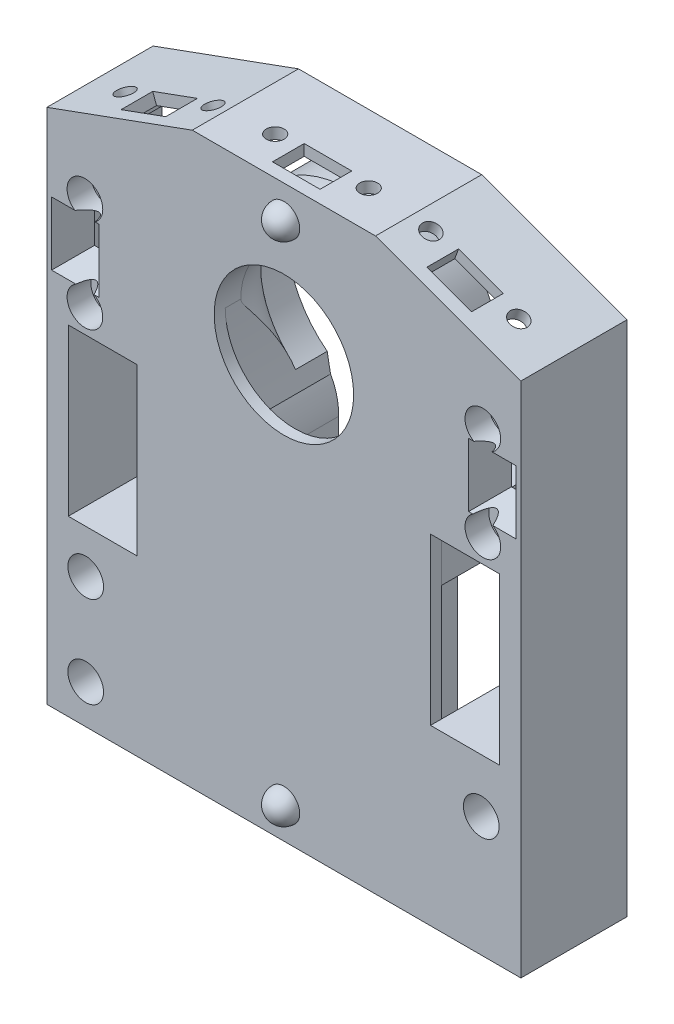
SolidWorks part; units mm, degrees
ref_plane "Front Plane" through (0, 0, 0) normal (0, 0, 1) x (1, 0, 0)
ref_plane "Top Plane" through (0, 0, 0) normal (0, 1, 0) x (1, 0, 0)
ref_plane "Right Plane" through (0, 0, 0) normal (1, 0, 0) x (0, 0, -1)
sketch "Sketch1" plane through (0, 0, 0) normal (0, 0, 1) x (1, 0, 0)
  line L5 (-16.4, -18.5) -> (43.4, -18.5)
  line L6 (-16.4, -18.5) -> (-16.4, 46.724)
  line L8 (43.4, -18.5) -> (43.4, 46.724)
  line L9 (1.9423, 53.4) -> (-16.4, 46.724)
  line L10 (1.9423, 53.4) -> (25.0577, 53.4)
  line L11 (-5, 24.3) -> (-5, 3.4)
  line L12 (25.0577, 53.4) -> (43.4, 46.724)
  line L13 (2.1891, 52) -> (24.8109, 52)
  line L14 (-15, -17.1) -> (42, -17.1) construction
  line L15 (-15, 30.4) -> (-15, -17.1) construction
  line L16 (42, -17.1) -> (42, 30.4) construction
  line L17 (-6.5, 21.65) -> (33.5, 21.65) construction
  line L18 (21.2, 52) -> (5.8, 52) construction
  line L19 (-13.9, 46.144) -> (2.1891, 52)
  line L20 (-15, 40.9) -> (-0.8, 40.9) construction
  line L21 (24.8109, 52) -> (40.9, 46.144)
  line L22 (27.8, 40.9) -> (42, 40.9) construction
  line L23 (-13.9, 46.144) -> (-13.9, 42.1)
  line L24 (-13.9, 42.1) -> (-5, 42.1)
  line L25 (-5, 42.1) -> (-5, 24.3)
  line L26 (-5, 24.3) -> (-13.7, 24.3)
  line L27 (-13.7, 24.3) -> (-13.7, 3.4)
  line L28 (-13.7, 3.4) -> (-5, 3.4)
  line L29 (-5, 18) -> (-5, 0) construction
  line L30 (-5, 3.4) -> (-5, -17.1)
  line L31 (-5, -17.1) -> (32, -17.1)
  line L32 (32, -17.1) -> (32, 3.4)
  line L33 (32, 18) -> (32, 0) construction
  line L34 (32, 3.4) -> (40.7, 3.4)
  line L35 (40.7, 3.4) -> (40.7, 24.3)
  line L36 (40.7, 24.3) -> (32, 24.3)
  line L37 (32, 24.3) -> (32, 42.1)
  line L38 (32, 42.1) -> (40.9, 42.1)
  line L39 (40.9, 42.1) -> (40.9, 46.144)
  line L52 (-15, 25.5) -> (-15, 40.9) construction
  line L53 (42, 40.9) -> (42, 25.5) construction
  line L54 (-13, 15.5) -> (-13, 12.5) construction
  line L55 (-0.8, 25.5) -> (-15, 25.5) construction
  line L56 (42, 25.5) -> (27.8, 25.5) construction
  line L57 (40, 15.118) -> (40, 12.882) construction
  line L58 (-5, 24.3) -> (2.2578, 24.3)
  line L59 (-5, 24.3) -> (-5, 18)
  line L60 (5, 18) -> (5, -17.1)
  line L61 (5, -17.1) -> (22, -17.1)
  line L62 (22, -17.1) -> (22, 18)
  line L63 (32, 24.3) -> (32, 3.4)
  line L64 (-5, 18) -> (5, 18)
  line L65 (-5, 23.5) -> (-5, 4.5) construction
  line L66 (22, 18) -> (32, 18)
  line L67 (32, 18) -> (32, 24.3)
  line L68 (32, 24.3) -> (24.7422, 24.3)
  arc A0 (27.3, 34.65) -> (-0.3, 34.65) centre (13.5, 34.65) ccw
  circle A1 centre (13.5, 34.65) radius 12.5 construction
  arc A2 (27.3, 34.65) -> (23.1, 21.65) centre (5.081, 34.65) cw
  arc A3 (22, 18) -> (23.1, 21.65) centre (27.8389, 18.2311) cw
  arc A4 (-0.3, 34.65) -> (3.9, 21.65) centre (21.919, 34.65) ccw
  arc A5 (3.9, 21.65) -> (5, 18) centre (-0.8389, 18.2311) cw
  point P2 (13.5, 52)
  point P5 (13.5, 53.4)
  dimension "D28" = 1.3
  dimension "D30" = 20.3
  dimension "D1" = 1.4
  dimension "D2" = 1.4
  dimension "D3" = 1.4
  dimension "D4" = 70
  dimension "D5" = 18.3423
  dimension "D6" = 70
  dimension "D7" = 18.3423
  dimension "D12" = 22.6217
  dimension "D13" = 160
  dimension "D14" = 160
  dimension "D15" = 2.5
  dimension "D16" = 2.5
  dimension "D17" = 0
  dimension "D18" = 1.2
  dimension "D19" = 1.2
  dimension "D20" = 10
  dimension "D21" = 10
  dimension "D22" = 0.7
  dimension "D23" = 1.2
  dimension "D24" = 1.2
  dimension "D25" = 0.7
  dimension "D26" = 20.5
  dimension "D27" = 20.5
  dimension "D29" = 20.3
sketch "Sketch2" plane through (19.6148, 53.8912, 0) normal (0.342, 0.9397, 0) x (0.9397, -0.342, 0)
  line L0 (15.4737, 3.2) -> (15.4737, 1.2) construction
  line L1 (19.4117, 7.9) -> (19.4117, 7.6) construction
  line L2 (19.9117, 7.1) -> (16.7617, 7.1)
  line L3 (19.9117, 7.1) -> (19.9117, 9.7)
  line L4 (19.9117, 9.7) -> (16.7617, 9.7)
  line L5 (16.7617, 7.1) -> (16.7617, 9.7)
  line L6 (13.7117, 5.5) -> (11.1117, 5.5)
  line L7 (13.7117, 5.5) -> (13.7117, 8.8)
  line L8 (13.7117, 8.8) -> (11.1117, 8.8)
  line L9 (11.1117, 5.5) -> (11.1117, 8.8)
  line L10 (18.6417, 7.6) -> (19.3817, 7.6) construction
  line L11 (18.6417, 9.2) -> (19.3817, 9.2) construction
  line L12 (17.2617, 8.065) -> (17.2617, 7.935) construction
  line L13 (12.9117, 8.3) -> (11.9117, 8.3) construction
  line L14 (13.2117, 6) -> (12.9117, 6) construction
  line L15 (13.2117, 8.3) -> (13.2117, 7.5) construction
  line L16 (11.6117, 8.3) -> (11.6117, 7.5) construction
  line L17 (10.4737, 4.2) -> (16.4737, 4.2)
  line L18 (10.4737, 4.2) -> (10.4737, 0.2)
  line L19 (10.4737, 0.2) -> (16.4737, 0.2)
  line L20 (16.4737, 4.2) -> (16.4737, 0.2)
  line L21 (11.4737, 1.2) -> (11.4737, 3.2) construction
  line L22 (11.4737, 3.2) -> (15.4737, 3.2) construction
  line L23 (15.4737, 1.2) -> (11.4737, 1.2) construction
  circle A0 centre (19.4117, 3.4) radius 1.125
  circle A1 centre (7.6117, 3.4) radius 1.125
  dimension "D13" = 2.25
  dimension "D14" = 2.25
  dimension "D1" = 0.5
  dimension "D2" = 0.5
  dimension "D3" = 0.5
  dimension "D4" = 0.5
  dimension "D5" = 0.5
  dimension "D6" = 0.5
  dimension "D7" = 0.5
  dimension "D8" = 0.5
  dimension "D9" = 1
  dimension "D10" = 1
  dimension "D11" = 1
  dimension "D12" = 1
sketch "Sketch3" plane through (0, 52, 0) normal (0, 1, 0) x (1, 0, 0)
  line L0 (13.2, 6.77) -> (13.2, 6.03) construction
  line L1 (19.9, 7.1) -> (16.75, 7.1)
  line L2 (19.9, 7.1) -> (19.9, 9.7)
  line L3 (19.9, 9.7) -> (16.75, 9.7)
  line L4 (16.75, 7.1) -> (16.75, 9.7)
  line L5 (13.7, 5.5) -> (11.1, 5.5)
  line L6 (13.7, 5.5) -> (13.7, 8.8)
  line L7 (13.7, 8.8) -> (11.1, 8.8)
  line L8 (11.1, 5.5) -> (11.1, 8.8)
  line L9 (13.2, 6) -> (12.9, 6) construction
  line L10 (13.155, 8.3) -> (12.945, 8.3) construction
  line L11 (11.6, 8.3) -> (11.6, 7.5) construction
  line L12 (19.4, 9.2) -> (19.4, 8.9) construction
  line L13 (18.63, 9.2) -> (19.37, 9.2) construction
  line L14 (18.63, 7.6) -> (19.37, 7.6) construction
  line L15 (17.25, 8.7) -> (17.25, 8.1) construction
  line L16 (11.462, 1.2) -> (11.462, 3.2) construction
  line L17 (10.462, 4.2) -> (16.462, 4.2)
  line L18 (10.462, 4.2) -> (10.462, 0.2)
  line L19 (10.462, 0.2) -> (16.462, 0.2)
  line L20 (16.462, 4.2) -> (16.462, 0.2)
  line L21 (15.462, 3.2) -> (15.462, 1.2) construction
  line L22 (11.462, 3.2) -> (15.462, 3.2) construction
  line L24 (15.462, 1.2) -> (11.462, 1.2) construction
  circle A0 centre (19.4, 3.4) radius 1.125
  circle A1 centre (7.6, 3.4) radius 1.125
  dimension "D13" = 2.25
  dimension "D14" = 2.25
  dimension "D1" = 0.5
  dimension "D2" = 0.5
  dimension "D3" = 0.5
  dimension "D4" = 0.5
  dimension "D5" = 0.5
  dimension "D6" = 0.5
  dimension "D7" = 0.5
  dimension "D8" = 0.5
  dimension "D9" = 1
  dimension "D10" = 1
  dimension "D11" = 1
  dimension "D12" = 1
sketch "Sketch4" plane through (-16.4564, 45.2136, 0) normal (-0.342, 0.9397, 0) x (0.9397, 0.342, 0)
  line L0 (11.56, 8.3) -> (11.56, 7.5) construction
  line L1 (12.06, 5.5) -> (9.46, 5.5)
  line L2 (12.06, 5.5) -> (12.06, 8.8)
  line L3 (12.06, 8.8) -> (9.46, 8.8)
  line L4 (9.46, 5.5) -> (9.46, 8.8)
  line L5 (18.26, 7.1) -> (15.11, 7.1)
  line L6 (18.26, 7.1) -> (18.26, 9.7)
  line L7 (18.26, 9.7) -> (15.11, 9.7)
  line L8 (15.11, 7.1) -> (15.11, 9.7)
  line L9 (11.56, 6) -> (11.26, 6) construction
  line L10 (9.96, 8.3) -> (9.96, 7.5) construction
  line L11 (10.215, 8.3) -> (10.005, 8.3) construction
  line L12 (16.99, 9.2) -> (17.73, 9.2) construction
  line L13 (17.76, 9.2) -> (17.76, 8.9) construction
  line L14 (15.61, 8.7) -> (15.61, 8.1) construction
  line L15 (16.99, 7.6) -> (17.73, 7.6) construction
  line L17 (14.822, 0.2) -> (8.822, 0.2)
  line L18 (14.822, 0.2) -> (14.822, 4.2)
  line L19 (14.822, 4.2) -> (8.822, 4.2)
  line L20 (8.822, 0.2) -> (8.822, 4.2)
  line L21 (13.822, 3.2) -> (13.822, 1.2) construction
  line L23 (9.822, 1.2) -> (9.822, 3.2) construction
  line L24 (9.822, 3.2) -> (13.822, 3.2) construction
  line L25 (13.822, 1.2) -> (9.822, 1.2) construction
  circle A0 centre (17.76, 3.4) radius 1.125
  circle A1 centre (5.96, 3.4) radius 1.125
  dimension "D13" = 2.25
  dimension "D14" = 2.25
  dimension "D1" = 0.5
  dimension "D2" = 0.5
  dimension "D3" = 0.5
  dimension "D4" = 0.5
  dimension "D5" = 0.5
  dimension "D6" = 0.5
  dimension "D7" = 0.5
  dimension "D8" = 0.5
  dimension "D9" = 1
  dimension "D10" = 1
  dimension "D11" = 1
  dimension "D12" = 1
ref_plane "Plane1" through (13.5, 0, 0) normal (1, 0, 0) x (0, 0, -1)
extrude "Boss-Extrude5" add sketch "Sketch1" against normal blind 12 contours L12 L10 L9 L6 L5 L8 L39 L38 L37 L36 L35 L34 L32 L31 L30 L28 L27 L26 L25 L24 L23 L19 L13 L21 | A5 A4 L58 L11 L64 | A3 L66 L63 L68 A2 region at (-15.4648, 14.112, 0) region at (-0.4625, 20.9721, 0) region at (27.4625, 20.9721, 0)
extrude "Boss-Extrude6" add sketch "Sketch1<6>" along normal blind 1.4 contours L12 L10 L9 L6 L5 L8 L39 L38 L37 L36 L35 L34 L32 L31 L30 L28 L27 L26 L25 L24 L23 L19 L13 L21 | A5 A4 A0 A2 A3 L62 L31 L32 L34 L35 L36 L37 L38 L39 L21 L13 L19 L23 L24 L25 L26 L27 L28 L30 L60 | A4 A5 L60 L31 L62 A3 A2 A0 | L64 L11 L30 L31 L60 | L66 L62 L31 L32 L63 | A5 A4 L58 L11 L64 | A3 L66 L63 L68 A2 region at (-15.4648, 14.112, 0) region at (-0.4625, 20.9721, 0) region at (-4.386, 33.2, 0) region at (0, 0.45, 0) region at (13.5, 17.8317, 0) region at (27, 0.45, 0) region at (27.4625, 20.9721, 0)
sketch "Sketch1<6>" plane through (0, 0, 0) normal (0, 0, 1) x (1, 0, 0) same geometry as "Sketch1"
extrude "Boss-Extrude7" add sketch "Sketch1<7>" against normal blind 12 contours A4 A5 L60 L31 L62 A3 A2 A0 region at (13.5, 17.8317, 0)
sketch "Sketch1<7>" plane through (0, 0, 0) normal (0, 0, 1) x (1, 0, 0) same geometry as "Sketch1"
sketch "Sketch5" plane through (13.5, 0, 0) normal (1, 0, 0) x (0, 0, -1)
  line L0 (12, 47.65) -> (12, 34.65)
  line L3 (12, 53.4) -> (12, 46.724) construction
  line L4 (1.9615, 43.45) -> (1.9615, 34.65)
  line L5 (2.9615, 37.5838) -> (2.9615, 31.7162) construction
  line L7 (-4.0592, 34.65) -> (24.6521, 34.65) construction
  line L8 (7, 48.45) -> (0, 48.45)
  line L9 (12, 48.45) -> (0, 48.45) construction
  line L10 (0, 48.45) -> (0, 44.45)
  line L11 (0, 42.1) -> (0, 46.144) construction
  line L12 (0, 52) -> (0, 46.144) construction
  line L13 (12, 47.65) -> (8, 47.65)
  line L14 (12, 47.15) -> (11.6116, 47.15) construction
  line L15 (1.9615, 34.65) -> (12, 34.65)
  arc A0 (8, 47.65) -> (1.9615, 43.45) centre (1.5799, 50.4396) cw
  arc A2 (7, 48.45) -> (0, 44.45) centre (0.6607, 51.4187) cw
  dimension "D5" = 7
  dimension "D8" = 7
  dimension "D1" = 1
  dimension "D2" = 0.5
  dimension "D6" = 7
  dimension "D7" = 4
  dimension "D9" = 5
  dimension "D10" = 8
revolve "Cut-Revolve5" cut sketch "Sketch5" angle 360 about L7 region at (13.5, 40.3885, -7.4006) reverse direction yes
sketch "Sketch6" plane through (0, 0, -3) normal (0, 0, 1) x (1, 0, 0)
  line L0 (42, 40.9) -> (42, 25.5) construction
  line L1 (27.8, 42.1) -> (42.25, 42.1)
  line L2 (27.8, 42.1) -> (27.8, 24.3)
  line L3 (27.8, 24.3) -> (42.25, 24.3)
  line L4 (42.25, 42.1) -> (42.25, 24.3)
  line L5 (27.8, 25.5) -> (27.8, 40.9) construction
  line L6 (32, 42.1) -> (40.9, 42.1) construction
  line L7 (40.7, 24.3) -> (32, 24.3) construction
  line L8 (38.8, 35.162) -> (40.8, 35.162) construction
  line L9 (32.3, 39.6) -> (34.9, 39.6)
  line L10 (32.3, 39.6) -> (32.3, 36.45)
  line L11 (32.3, 36.45) -> (34.9, 36.45)
  line L12 (34.9, 39.6) -> (34.9, 36.45)
  line L13 (33.2, 33.4) -> (36.5, 33.4)
  line L14 (33.2, 33.4) -> (33.2, 30.8)
  line L15 (33.2, 30.8) -> (36.5, 30.8)
  line L16 (36.5, 33.4) -> (36.5, 30.8)
  line L17 (37.8, 36.162) -> (41.8, 36.162)
  line L18 (37.8, 36.162) -> (37.8, 30.162)
  line L19 (37.8, 30.162) -> (41.8, 30.162)
  line L20 (41.8, 36.162) -> (41.8, 30.162)
  line L21 (40.8, 31.162) -> (38.8, 31.162) construction
  line L22 (40.8, 35.162) -> (40.8, 31.162) construction
  line L23 (38.8, 31.162) -> (38.8, 35.162) construction
  line L24 (42, 30.4) -> (-15, 30.4) construction
  line L25 (-0.8, 42.1) -> (-15.25, 42.1)
  line L26 (-0.8, 42.1) -> (-0.8, 24.3)
  line L27 (-0.8, 24.3) -> (-15.25, 24.3)
  line L28 (-15.25, 42.1) -> (-15.25, 24.3)
  line L29 (-9.5, 35.6) -> (-6.2, 35.6)
  line L30 (-9.5, 35.6) -> (-9.5, 33)
  line L31 (-9.5, 33) -> (-6.2, 33)
  line L32 (-6.2, 35.6) -> (-6.2, 33)
  line L33 (-7.9, 30.4) -> (-5.3, 30.4)
  line L34 (-7.9, 30.4) -> (-7.9, 26.8)
  line L35 (-7.9, 26.8) -> (-5.3, 26.8)
  line L36 (-5.3, 30.4) -> (-5.3, 26.8)
  line L37 (-11.8, 31.238) -> (-13.8, 31.238) construction
  line L38 (-14.8, 36.238) -> (-10.8, 36.238)
  line L39 (-14.8, 36.238) -> (-14.8, 30.238)
  line L40 (-14.8, 30.238) -> (-10.8, 30.238)
  line L41 (-10.8, 36.238) -> (-10.8, 30.238)
  line L42 (-13.8, 31.238) -> (-13.8, 35.238) construction
  line L43 (-11.8, 35.238) -> (-11.8, 31.238) construction
  line L45 (-13.8, 35.238) -> (-11.8, 35.238) construction
  line L46 (-15, 25.5) -> (-15, 40.9) construction
  line L47 (-13.9, 42.1) -> (-5, 42.1) construction
  line L48 (-5, 24.3) -> (-13.7, 24.3) construction
  line L49 (-0.8, 40.9) -> (-0.8, 25.5) construction
  line L50 (-9, 34.8) -> (-9, 35.1) construction
  line L51 (-6.7, 34.845) -> (-6.7, 35.055) construction
  line L52 (-8.23, 35.1) -> (-8.97, 35.1) construction
  line L53 (-8.23, 33.5) -> (-8.97, 33.5) construction
  line L54 (-5.8, 28.07) -> (-5.8, 27.33) construction
  line L55 (-7.1, 27.3) -> (-7.4, 27.3) construction
  line L56 (-7.4, 28.07) -> (-7.4, 27.33) construction
  line L57 (34.4, 38.33) -> (34.4, 39.07) construction
  line L58 (32.8, 38.33) -> (32.8, 39.07) construction
  line L59 (32.8, 39.1) -> (33.1, 39.1) construction
  line L60 (33.3, 36.95) -> (33.9, 36.95) construction
  line L61 (36, 32.9) -> (36, 32.6) construction
  line L62 (33.7, 31.3) -> (34.5, 31.3) construction
  line L63 (33.7, 32.6) -> (33.7, 31.6) construction
  line L64 (33.7, 32.9) -> (34.5, 32.9) construction
  circle A0 centre (-11.6, 39.1) radius 1.125
  circle A1 centre (-11.6, 27.3) radius 1.125
  circle A2 centre (38.6, 39.1) radius 1.125
  circle A3 centre (38.6, 27.3) radius 1.125
  dimension "D9" = 1
  dimension "D10" = 1
  dimension "D11" = 1
  dimension "D12" = 1
  dimension "D32" = 2.25
  dimension "D33" = 2.25
  dimension "D34" = 2.25
  dimension "D35" = 2.25
  dimension "D1" = 0.25
  dimension "D2" = 0
  dimension "D3" = 0
  dimension "D4" = 0
  dimension "D5" = 1
  dimension "D6" = 1
  dimension "D7" = 1
  dimension "D8" = 1
  dimension "D13" = 0.25
  dimension "D14" = 0
  dimension "D15" = 0
  dimension "D16" = 0
  dimension "D17" = 0.5
  dimension "D18" = 0.5
  dimension "D19" = 0.5
  dimension "D20" = 0.5
  dimension "D21" = 0.5
  dimension "D22" = 0.5
  dimension "D23" = 0.5
  dimension "D24" = 0.5
  dimension "D25" = 0.5
  dimension "D26" = 0.5
  dimension "D27" = 0.5
  dimension "D28" = 0.5
  dimension "D29" = 0.5
  dimension "D30" = 0.5
  dimension "D31" = 0.5
revolve "Cut-Revolve6" cut sketch "Sketch5<6>" angle 90 about L7 region at (13.5, 46.7453, -2.8075) other way angle 90
sketch "Sketch5<6>" plane through (13.5, 0, 0) normal (1, 0, 0) x (0, 0, -1) same geometry as "Sketch5"
extrude "Cut-Extrude1" cut sketch "Sketch2" along normal blind 1 contours L5 L2 L3 L4 | L9 L6 L7 L8 region at (36.8456, 47.6197, -8.4) region at (31.2779, 49.6462, -7.15)
extrude "Cut-Extrude2" cut sketch "Sketch2<3>" along normal blind 1.4 contours L20 L17 L18 L19 region at (32.2759, 49.2829, -2.2)
sketch "Sketch2<3>" plane through (19.6148, 53.8912, 0) normal (0.342, 0.9397, 0) x (0.9397, -0.342, 0) same geometry as "Sketch2"
extrude "Cut-Extrude3" cut sketch "Sketch3" along normal blind 1 contours L8 L7 L6 L5 | L4 L3 L2 L1
extrude "Cut-Extrude4" cut sketch "Sketch3<3>" along normal blind 1.4 contours L19 L20 L17 L18
sketch "Sketch3<3>" plane through (0, 52, 0) normal (0, 1, 0) x (1, 0, 0) same geometry as "Sketch3"
extrude "Cut-Extrude5" cut sketch "Sketch4" along normal blind 1 contours L5 L8 L7 L6 | L1 L4 L3 L2
extrude "Cut-Extrude6" cut sketch "Sketch4<3>" along normal blind 1.4 contours L19 L20 L17 L18
sketch "Sketch4<3>" plane through (-16.4564, 45.2136, 0) normal (-0.342, 0.9397, 0) x (0.9397, 0.342, 0) same geometry as "Sketch4"
extrude "Cut-Extrude7" cut sketch "Sketch6" along normal blind 1 contours L10 L11 L12 L9 | L14 L15 L16 L13 | L30 L31 L32 L29 | L34 L35 L36 L33
sketch "Sketch8" plane through (0, 0, 1.4) normal (0, 0, 1) x (1, 0, 0)
  line L0 (-11.8, 35.238) -> (-11.8, 31.238) construction
  line L1 (-9.8, 29.238) -> (-15.8, 29.238)
  line L2 (-9.8, 29.238) -> (-9.8, 37.238)
  line L3 (-9.8, 37.238) -> (-15.8, 37.238)
  line L4 (-15.8, 29.238) -> (-15.8, 37.238)
  line L5 (-11.8, 31.238) -> (-13.8, 31.238) construction
  line L6 (-13.8, 35.238) -> (-11.8, 35.238) construction
  line L7 (-13.8, 31.238) -> (-13.8, 35.238) construction
  line L8 (38.8, 35.162) -> (40.8, 35.162) construction
  line L9 (36.8, 37.162) -> (42.8, 37.162)
  line L10 (36.8, 37.162) -> (36.8, 29.162)
  line L11 (36.8, 29.162) -> (42.8, 29.162)
  line L12 (42.8, 37.162) -> (42.8, 29.162)
  line L14 (40.8, 35.162) -> (40.8, 31.162) construction
  line L15 (38.8, 31.162) -> (38.8, 35.162) construction
  line L16 (40.8, 31.162) -> (38.8, 31.162) construction
  dimension "D1" = 2
  dimension "D2" = 2
  dimension "D3" = 2
  dimension "D4" = 2
  dimension "D5" = 2
  dimension "D6" = 2
  dimension "D7" = 2
  dimension "D8" = 2
loft "Cut-Loft3" cut section "Sketch6<8>" section "Sketch8<7>" connector at (37.8, 36.162, -3) connector at (36.8, 37.162, 1.4)
sketch "Sketch6<8>" plane through (0, 0, -3) normal (0, 0, 1) x (1, 0, 0) same geometry as "Sketch6"
sketch "Sketch8<7>" plane through (0, 0, 1.4) normal (0, 0, 1) x (1, 0, 0) same geometry as "Sketch8"
loft "Cut-Loft4" cut section "Sketch6<9>" section "Sketch8<6>" connector at (-14.8, 36.238, -3) connector at (-15.8, 37.238, 1.4)
sketch "Sketch6<9>" plane through (0, 0, -3) normal (0, 0, 1) x (1, 0, 0) same geometry as "Sketch6"
sketch "Sketch8<6>" plane through (0, 0, 1.4) normal (0, 0, 1) x (1, 0, 0) same geometry as "Sketch8"
extrude "Cut-Extrude9" cut sketch "Sketch6<10>" against normal up to surface (9 mm away) contours L4 L3 L2 L1 | L25 L28 L27 L26 up to face at (0.5, 34.65, -12)
sketch "Sketch6<10>" plane through (0, 0, -3) normal (0, 0, 1) x (1, 0, 0) same geometry as "Sketch6"
extrude "Cut-Extrude10" cut sketch "Sketch2<4>" along normal up to next (1.4 mm away) contours A0 | A1
sketch "Sketch2<4>" plane through (19.6148, 53.8912, 0) normal (0.342, 0.9397, 0) x (0.9397, -0.342, 0) same geometry as "Sketch2"
extrude "Cut-Extrude11" cut sketch "Sketch3<4>" along normal up to next (1.4 mm away) contours A1 | A0
sketch "Sketch3<4>" plane through (0, 52, 0) normal (0, 1, 0) x (1, 0, 0) same geometry as "Sketch3"
extrude "Cut-Extrude12" cut sketch "Sketch4<4>" along normal up to next (1.4 mm away) contours A1 | A0
sketch "Sketch4<4>" plane through (-16.4564, 45.2136, 0) normal (-0.342, 0.9397, 0) x (0.9397, 0.342, 0) same geometry as "Sketch4"
extrude "Cut-Extrude13" cut sketch "Sketch6<11>" along normal blind 1.4 contours A1 | A0 | A3 | A2
sketch "Sketch6<11>" plane through (0, 0, -3) normal (0, 0, 1) x (1, 0, 0) same geometry as "Sketch6"
sketch "Sketch9" plane through (0, 0, 1.4) normal (0, 0, 1) x (1, 0, 0)
  circle A0 centre (-11.6, 39.1) radius 2.25
  circle A1 centre (-11.6, 27.3) radius 2.25
  circle A2 centre (38.6, 39.1) radius 2.25
  circle A3 centre (38.6, 27.3) radius 2.25
  dimension "D1" = 4.5
  dimension "D2" = 4.5
  dimension "D3" = 4.5
  dimension "D4" = 4.5
ref_plane "Screw Head Surface At Bottom" through (0, 0, -1.6) normal (0, 0, -1) x (-1, 0, 0)
extrude "Cut-Extrude14" cut sketch "Sketch9" against normal up to surface (3 mm away) up to plane "Screw Head Surface At Bottom"
sketch "Sketch10" plane through (0, 0, 1.4) normal (0, 0, 1) x (1, 0, 0)
  circle A0 centre (13.5, 34.65) radius 8.8
  dimension "D1" = 17.6
ref_plane "Fan Hole Surface" through (0, 0, -1.9615) normal (0, 0, -1) x (-1, 0, 0)
extrude "Cut-Extrude15" cut sketch "Sketch10" against normal up to surface (3.3615 mm away) up to plane "Fan Hole Surface"
sketch "Sketch12" plane through (0, 0, -12) normal (0, 0, -1) x (-1, 0, 0)
  line L0 (-22, -17.1) -> (-22, -18.5)
  line L1 (16.4, -18.5) -> (-43.4, -18.5) construction
  line L2 (-22, -18.5) -> (-5, -18.5)
  line L3 (-5, -18.5) -> (-5, -17.1)
  line L6 (-5, 18) -> (-5, -17.1) construction
  line L7 (-22, -17.1) -> (-22, 18) construction
  line L8 (-5, 18) -> (-5, -17.1)
  line L9 (-22, -17.1) -> (-22, 18)
  line L10 (-7, -18.5) -> (-7, -17.1)
  line L11 (-7, 17.9633) -> (-7, -17.1)
  line L12 (-20, -17.1) -> (-20, 17.9633)
  line L13 (-20, -17.1) -> (-20, -18.5)
  line L15 (-20, -17.1) -> (-20, -18.5) construction
  line L16 (-7, -18.5) -> (-7, -17.1) construction
  arc A8 (0.3, 34.65) -> (-27.3, 34.65) centre (-13.5, 34.65) ccw construction
  arc A11 (-3.9, 21.65) -> (-5, 18) centre (0.8389, 18.2311) ccw construction
  arc A14 (-22, 18) -> (-23.1, 21.65) centre (-27.8389, 18.2311) ccw construction
  arc A15 (0.3, 34.65) -> (-27.3, 34.65) centre (-13.5, 34.65) ccw
  arc A16 (-3.9, 21.65) -> (0.3, 34.65) centre (-21.919, 34.65) ccw construction
  arc A17 (-27.3, 34.65) -> (-23.1, 21.65) centre (-5.081, 34.65) ccw construction
  arc A18 (-3.9, 21.65) -> (-5, 18) centre (0.8389, 18.2311) ccw
  arc A19 (-3.9, 21.65) -> (0.3, 34.65) centre (-21.919, 34.65) ccw
  arc A20 (-27.3, 34.65) -> (-23.1, 21.65) centre (-5.081, 34.65) ccw
  arc A21 (-22, 18) -> (-23.1, 21.65) centre (-27.8389, 18.2311) ccw
  arc A22 (-5.5219, 22.8202) -> (-7, 17.9633) centre (0.8389, 18.2311) ccw
  arc A23 (-5.5219, 22.8202) -> (-1.7, 34.65) centre (-21.919, 34.65) ccw
  arc A24 (-1.7, 34.65) -> (-25.3, 34.65) centre (-13.5, 34.65) ccw
  arc A25 (-25.3, 34.65) -> (-21.4781, 22.8202) centre (-5.081, 34.65) ccw
  arc A26 (-20, 17.9633) -> (-21.4781, 22.8202) centre (-27.8389, 18.2311) ccw
  arc A27 (-22, 18) -> (-23.1, 21.65) centre (-27.8389, 18.2311) ccw construction
  arc A28 (-3.9, 21.65) -> (-5, 18) centre (0.8389, 18.2311) ccw construction
  circle A33 centre (-13.5, 34.65) radius 8.8 construction
  arc A34 (-25.3, 34.65) -> (-21.4781, 22.8202) centre (-5.081, 34.65) ccw construction
  circle A35 centre (-13.5, 34.65) radius 8.8
  arc A36 (-22.3, 34.65) -> (-20, 17.9633) centre (39.3814, 34.65) ccw
  arc A37 (-7, 17.9633) -> (-4.7, 34.65) centre (-66.3814, 34.65) ccw
  circle M96 centre (-13.5, 34.65) radius 13
  dimension "D2" = 2
extrude "Cut-Extrude18" cut sketch "Sketch12" against normal up to surface (12 mm away) contours A26 L12 L13 L2 L10 L11 A22 | A37 A35 A36 M96 region at (13.5, 2.1128, -12) region at (13.5, 25.4102, -12) up to plane "Front Plane"
ref_plane "Dust Bin Mid Plane" through (13.5, 0, 0) normal (1, 0, 0) x (0, 0, -1)
sketch "Sketch14" plane through (13.5, 0, 0) normal (1, 0, 0) x (0, 0, -1)
  line L0 (0, 0) -> (0, 18)
  line L1 (5, 9) -> (0, 9)
  arc A0 (5, 9) -> (3.05, 12.6) centre (-0.2736, 8.4716) ccw
  arc A1 (0, 18) -> (3.05, 12.6) centre (7.1829, 18.4957) ccw
  dimension "D3" = 7.2
  dimension "D4" = 5.3
  dimension "D1" = 3.6
  dimension "D2" = 3.05
  dimension "D5" = 5
extrude "Boss-Extrude8" add sketch "Sketch14" along normal up to surface and the other way up to surface contours A1 L0 L1 A0 region at (13.5, 11.5093, -1.8672) up to face at (20, -0.2683, -6) other way up to face at (7, -0.2683, -6)
sketch "Sketch15" plane through (0, 9, 0) normal (0, -1, 0) x (1, 0, 0)
  line L0 (20, 0) -> (20, -12) construction
  line L1 (20, 0) -> (7, 0) construction
  line L2 (7, 0) -> (7, -12) construction
  circle A0 centre (17, -2.5) radius 1.75
  circle A1 centre (10, -2.5) radius 1.75
  dimension "D2" = 3.5
  dimension "D4" = 3.5
  dimension "D1" = 3
  dimension "D3" = 2.5
  dimension "D5" = 3
  dimension "D6" = 2.5
extrude "Cut-Extrude19" cut sketch "Sketch15" against normal blind 1.5
sketch "Sketch16" plane through (219.8396, 130.5468, -3.6) normal (0, 0, -1) x (-1, 0, 0)
  circle A0 centre (181.4396, -133.8968) radius 2.25
  circle A1 centre (181.4396, -133.8968) radius 1.125
  dimension "D1" = 4.5
  dimension "D2" = 2.25
extrude "Cut-Extrude20" cut sketch "Sketch16" along normal through all contours A1 region at (38.4, -3.35, -3.6)
extrude "Cut-Extrude21" cut sketch "Sketch16<3>" against normal through all contours A1 | A0 A1 region at (40.5864, -3.35, -3.6) region at (38.4, -3.35, -3.6)
sketch "Sketch16<3>" plane through (219.8396, 130.5468, -3.6) normal (0, 0, -1) x (-1, 0, 0) same geometry as "Sketch16"
sketch "Sketch17" plane through (219.8396, 130.5468, -7.7002) normal (0, 0, -1) x (-1, 0, 0)
  circle A0 centre (231.3396, -132.6468) radius 2.25
  circle A1 centre (231.3396, -132.6468) radius 1.125
  circle A2 centre (231.3396, -144.1468) radius 2.25
  circle A3 centre (231.3396, -144.1468) radius 1.125
  dimension "D1" = 4.5
  dimension "D3" = 4.5
  dimension "D2" = 2.25
  dimension "D4" = 2.25
extrude "Cut-Extrude22" cut sketch "Sketch17" along normal through all contours A1 | A3 region at (-11.5, -2.1, -7.7002) region at (-11.5, -13.6, -7.7002)
extrude "Cut-Extrude23" cut sketch "Sketch17<3>" against normal through all contours A1 | A3 | A0 A1 | A2 A3 region at (-9.3136, -2.1, -7.7002) region at (-11.5, -2.1, -7.7002) region at (-9.3136, -13.6, -7.7002) region at (-11.5, -13.6, -7.7002)
sketch "Sketch17<3>" plane through (219.8396, 130.5468, -7.7002) normal (0, 0, -1) x (-1, 0, 0) same geometry as "Sketch17"
sketch "Sketch18" plane through (0, 0, 1.4) normal (0, 0, 1) x (1, 0, 0)
  line L0 (11.5, 49.4) -> (15.5, 49.4)
  line L1 (1.9423, 53.4) -> (25.0577, 53.4) construction
  line L2 (11.5, -14.5) -> (15.5, -14.5)
  line L3 (43.4, -18.5) -> (-16.4, -18.5) construction
  arc A0 (15.5, 49.4) -> (11.5, 49.4) centre (13.5, 49.4) ccw
  arc A1 (15.5, -14.5) -> (11.5, -14.5) centre (13.5, -14.5) ccw
  dimension "D2" = 4
  dimension "D3" = 4
  dimension "D1" = 4
  dimension "D4" = 4
revolve "Revolve1" add sketch "Sketch18" angle 180 about L0 region at (13.5, 50.2488, 1.4)
revolve "Revolve2" add sketch "Sketch18<3>" angle 180 about L2 region at (13.5, -13.6512, 1.4)
sketch "Sketch18<3>" plane through (0, 0, 1.4) normal (0, 0, 1) x (1, 0, 0) same geometry as "Sketch18"
equation "\"M2_screw_head_hole\"= 4.5"
equation "\"M2_screw_shaft_hole\"=2.25"
equation "\"D1@Sketch9\"=\"M2_screw_head_hole\""
equation "\"D4@Sketch9\"=\"M2_screw_head_hole\""
equation "\"D2@Sketch9\"=\"M2_screw_head_hole\""
equation "\"D3@Sketch9\"=\"M2_screw_head_hole\""
equation "\"D14@Sketch2\"=\"M2_screw_shaft_hole\""
equation "\"D13@Sketch2\"=\"M2_screw_shaft_hole\""
equation "\"D13@Sketch3\"=\"M2_screw_shaft_hole\""
equation "\"D14@Sketch3\"=\"M2_screw_shaft_hole\""
equation "\"D14@Sketch4\"=\"M2_screw_shaft_hole\""
equation "\"D13@Sketch4\"=\"M2_screw_shaft_hole\""
equation "\"D34@Sketch6\"=\"M2_screw_shaft_hole\""
equation "\"D35@Sketch6\"=\"M2_screw_shaft_hole\""
equation "\"D32@Sketch6\"=\"M2_screw_shaft_hole\""
equation "\"D33@Sketch6\"=\"M2_screw_shaft_hole\""
equation "\"D1@Sketch16\"=\"M2_screw_head_hole\""
equation "\"D2@Sketch16\"=\"M2_screw_shaft_hole\""
equation "\"D1@Sketch17\"=\"M2_screw_head_hole\""
equation "\"D2@Sketch17\"=\"M2_screw_shaft_hole\""
equation "\"D3@Sketch17\"=\"M2_screw_head_hole\""
equation "\"D4@Sketch17\"=\"M2_screw_shaft_hole\""
